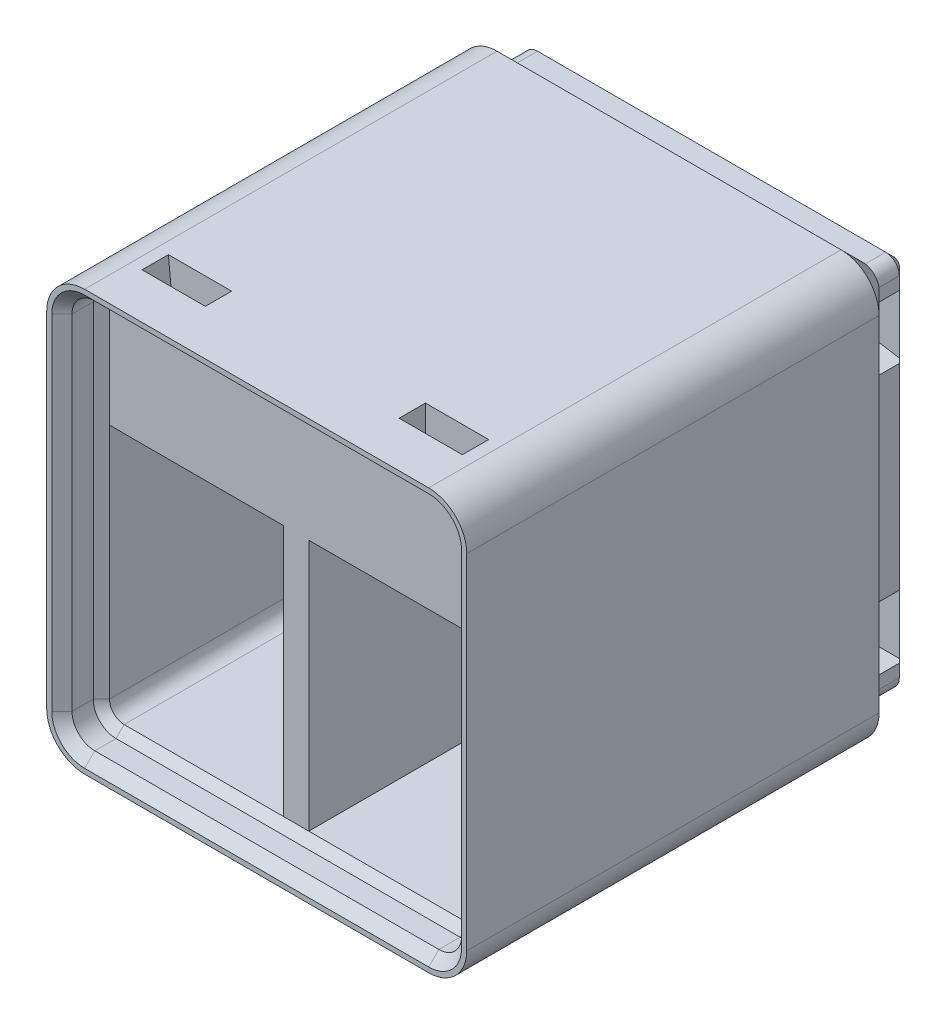
SolidWorks part; units mm, degrees
ref_plane "Front Plane" through (0, 0, 0) normal (0, 0, 1) x (1, 0, 0)
ref_plane "Top Plane" through (0, 0, 0) normal (0, 1, 0) x (1, 0, 0)
ref_plane "Right Plane" through (0, 0, 0) normal (1, 0, 0) x (0, 0, -1)
sketch "Sketch1" plane through (0, 0, 0) normal (0, 0, 1) x (1, 0, 0)
  line L1 (18.55, 18.55) -> (-18.55, 18.55)
  line L2 (18.55, 18.55) -> (18.55, -18.55)
  line L3 (18.55, -18.55) -> (-18.55, -18.55)
  line L4 (-18.55, 18.55) -> (-18.55, -18.55)
  line L5 (18.55, 18.55) -> (-18.55, -18.55) construction
  line L6 (18.55, -18.55) -> (-18.55, 18.55) construction
  point P0 (0, 0)
  dimension "D1" = 37.1
extrude "Boss-Extrude1" add sketch "Sketch1" along normal blind 2.6
sketch "Sketch2" plane through (0, 0, 2.6) normal (0, 0, 1) x (1, 0, 0)
  line L1 (-20.75, 20.75) -> (20.75, 20.75)
  line L2 (-20.75, 20.75) -> (-20.75, -20.75)
  line L3 (-20.75, -20.75) -> (20.75, -20.75)
  line L4 (20.75, 20.75) -> (20.75, -20.75)
  line L5 (-20.75, 20.75) -> (20.75, -20.75) construction
  line L6 (-20.75, -20.75) -> (20.75, 20.75) construction
  point P0 (0, 0)
  dimension "D1" = 41.5
extrude "Boss-Extrude2" add sketch "Sketch2" along normal blind 2.4
sketch "Sketch8" plane through (0, 0, 2.6) normal (0, 0, -1) x (-1, 0, 0)
  line L0 (-18.55, 18.55) -> (-18.55, 5.0094) construction
  line L1 (-18.55, -18.55) -> (-18.55, 18.55) construction
  line L2 (-14.8915, 10.3) -> (-18.55, 9.7)
  line L8 (12.7, 15.95) -> (-12.7, 15.95) construction
  line L9 (12.7, 9.45) -> (-12.7, 9.45) construction
  line L11 (-12.7, 15.95) -> (-18.55, 15.95)
  line L12 (-12.7, 12.7) -> (-12.7, -12.7)
  line L13 (-12.7, -12.7) -> (12.7, -12.7)
  line L14 (12.7, -12.7) -> (12.7, 12.7)
  line L15 (12.7, 12.7) -> (-12.7, 12.7)
  line L16 (-12.7, 9.45) -> (-12.7, -12.7) construction
  line L17 (-12.7, -12.7) -> (12.7, -12.7) construction
  line L18 (12.7, -12.7) -> (12.7, 12.7) construction
  line L19 (12.7, 12.7) -> (-12.7, 12.7) construction
  line L22 (-18.55, 15.95) -> (-18.55, 9.7)
  arc A0 (-12.7, 15.95) -> (-12.7, 9.45) centre (-12.7, 12.7) cw
  arc A1 (-12.7, 9.45) -> (-14.8915, 10.3) centre (-12.7, 12.7) cw
  dimension "D4" = 5.65
  dimension "D5" = 6.25
  dimension "D1" = 8.05
  dimension "D2" = 3.25
  dimension "D3" = 3.25
extrude "Base Magnet Slot" cut sketch "Sketch8" against normal blind 0.4 and the other way blind 2.2
fillet "Fillet1" radius 1.35 4 edges at (18.55, 18.55, 1.3) (18.55, -18.55, 1.3) (-18.55, -18.55, 1.3) (-18.55, 18.55, 1.3)
fillet "Fillet2" radius 3.75 4 edges at (20.75, -20.75, 3.8) (20.75, 20.75, 3.8) (-20.75, -20.75, 3.8) (-20.75, 20.75, 3.8)
chamfer "Chamfer1" distance 0.8 angle 45 8 edges at (-18.1546, 18.1546, 0) (-18.55, 0, 0) (-18.1546, -18.1546, 0) (0, -18.55, 0) (18.1546, -18.1546, 0) (18.55, 0, 0) (18.1546, 18.1546, 0) (0, 18.55, 0)
chamfer "Chamfer2" distance 2.4 angle 45 8 edges at (20.75, 0, 2.6) (19.6517, 19.6517, 2.6) (19.6517, -19.6517, 2.6) (0, 20.75, 2.6) (0, -20.75, 2.6) (-19.6517, 19.6517, 2.6) (-19.6517, -19.6517, 2.6) (-20.75, 0, 2.6)
sketch "Sketch4" plane through (0, 0, 0) normal (0, 0, -1) x (-1, 0, 0)
  line L9 (-12.7, -17) -> (-12.7, 17)
  line L10 (-12.7, -17) -> (-12.7, 17) construction
  line L12 (-17, 12.7) -> (17, 12.7)
  line L13 (-17, 12.7) -> (17, 12.7) construction
  circle A0 centre (-12.7, 12.7) radius 3.25
  circle A1 centre (12.7, 12.7) radius 3.25
  circle A2 centre (12.7, -12.7) radius 3.25
  circle A3 centre (-12.7, -12.7) radius 3.25
  dimension "D3" = 6.5
  dimension "D1" = 8.05
  dimension "D2" = 8.05
  dimension "D4" = 2
mirror "Mirror1" about plane through (0, 0, 0) normal (0, 1, 0) of "Base Magnet Slot"
mirror "Mirror2" about plane through (0, 0, 0) normal (1, 0, 0) of "Mirror1"
sketch "Sketch10" plane through (0, 0, 0) normal (0, 0, -1) x (-1, 0, 0)
  line L0 (-12.7, 12.7) -> (-7.7, 12.7) construction
  line L1 (-17, 12.7) -> (17, 12.7) construction
  line L2 (22.825, 0) -> (-22.825, 0) construction
  line L3 (-12.7, 13.7) -> (-7.7, 13.7)
  line L4 (-12.7, 11.7) -> (-7.7, 11.7)
  line L5 (-12.7, -12.7) -> (-7.7, -12.7) construction
  line L6 (-12.7, -13.7) -> (-7.7, -13.7)
  line L7 (-12.7, -11.7) -> (-7.7, -11.7)
  line L8 (0, 22.825) -> (0, -22.825) construction
  line L9 (12.7, 12.7) -> (7.7, 12.7) construction
  line L10 (12.7, 13.7) -> (7.7, 13.7)
  line L11 (12.7, 11.7) -> (7.7, 11.7)
  line L12 (12.7, -12.7) -> (7.7, -12.7) construction
  line L13 (12.7, -13.7) -> (7.7, -13.7)
  line L14 (12.7, -11.7) -> (7.7, -11.7)
  arc A0 (-12.7, 13.7) -> (-12.7, 11.7) centre (-12.7, 12.7) ccw
  arc A1 (-7.7, 11.7) -> (-7.7, 13.7) centre (-7.7, 12.7) ccw
  arc A2 (-12.7, -13.7) -> (-12.7, -11.7) centre (-12.7, -12.7) cw
  arc A3 (-7.7, -11.7) -> (-7.7, -13.7) centre (-7.7, -12.7) cw
  arc A4 (12.7, 13.7) -> (12.7, 11.7) centre (12.7, 12.7) cw
  arc A5 (7.7, 11.7) -> (7.7, 13.7) centre (7.7, 12.7) cw
  arc A6 (12.7, -13.7) -> (12.7, -11.7) centre (12.7, -12.7) ccw
  arc A7 (7.7, -11.7) -> (7.7, -13.7) centre (7.7, -12.7) ccw
  point P7 (-10.2, 12.7)
  point P14 (-10.2, -12.7)
  point P23 (10.2, 12.7)
  point P30 (10.2, -12.7)
extrude "Base Magnet Removal Slot" cut sketch "Sketch10" against normal up to surface (3 mm away) up to face at (15.1414, 12.5749, 3)
sketch "Sketch5" plane through (0, 0, 5) normal (0, 0, 1) x (1, 0, 0)
  line L0 (-20.75, -17) -> (-20.75, 17)
  line L1 (-20.75, -17) -> (-20.75, 17)
  line L8 (-18.45, -17) -> (-18.45, 17)
  line L9 (-17, 18.45) -> (17, 18.45)
  line L10 (18.45, 17) -> (18.45, -17)
  line L11 (17, -18.45) -> (-17, -18.45)
  line L12 (20.75, 17) -> (20.75, -17)
  line L13 (17, -20.75) -> (-17, -20.75)
  line L15 (-17, 20.75) -> (17, 20.75)
  line L18 (-17, 20.75) -> (17, 20.75) construction
  line L19 (20.75, 17) -> (20.75, -17) construction
  line L20 (17, -20.75) -> (-17, -20.75) construction
  line L22 (20.75, 17) -> (20.75, -17)
  line L23 (17, -20.75) -> (-17, -20.75)
  line L25 (-17, 20.75) -> (17, 20.75)
  arc A8 (-17, 18.45) -> (-18.45, 17) centre (-17, 17) ccw
  arc A9 (18.45, 17) -> (17, 18.45) centre (17, 17) ccw
  arc A10 (17, -18.45) -> (18.45, -17) centre (17, -17) ccw
  arc A11 (-18.45, -17) -> (-17, -18.45) centre (-17, -17) ccw
  arc A12 (17, -20.75) -> (20.75, -17) centre (17, -17) ccw
  arc A13 (-20.75, -17) -> (-17, -20.75) centre (-17, -17) ccw
  arc A14 (-17, 20.75) -> (-20.75, 17) centre (-17, 17) ccw
  arc A15 (20.75, 17) -> (17, 20.75) centre (17, 17) ccw
  arc A18 (-17, 20.75) -> (-20.75, 17) centre (-17, 17) ccw construction
  arc A19 (20.75, 17) -> (17, 20.75) centre (17, 17) ccw construction
  arc A20 (17, -20.75) -> (20.75, -17) centre (17, -17) ccw construction
  arc A21 (-20.75, -17) -> (-17, -20.75) centre (-17, -17) ccw construction
  arc A24 (17, -20.75) -> (20.75, -17) centre (17, -17) ccw
  arc A25 (-20.75, -17) -> (-17, -20.75) centre (-17, -17) ccw
  arc A26 (-17, 20.75) -> (-20.75, 17) centre (-17, 17) ccw
  arc A27 (20.75, 17) -> (17, 20.75) centre (17, 17) ccw
  dimension "D1" = 2.3
extrude "Boss-Extrude3" add sketch "Sketch5" along normal blind 36.85
sketch "Sketch12" plane through (0, 0, 41.85) normal (0, 0, 1) x (1, 0, 0)
  line L1 (18.45, -17) -> (18.45, 17) construction
  line L2 (17, 6.45) -> (-17, 6.45)
  line L3 (18.45, 6.45) -> (-18.45, 6.45)
  line L4 (17, 18.45) -> (-17, 18.45) construction
  line L5 (-18.45, 17) -> (-18.45, -17) construction
  line L6 (18.45, 6.45) -> (18.45, 17)
  line L7 (17, 18.45) -> (-17, 18.45)
  line L8 (-18.45, 17) -> (-18.45, 6.45)
  arc A0 (18.45, 17) -> (17, 18.45) centre (17, 17) ccw construction
  arc A1 (-17, 18.45) -> (-18.45, 17) centre (-17, 17) ccw construction
  arc A2 (18.45, 17) -> (17, 18.45) centre (17, 17) ccw
  arc A3 (-17, 18.45) -> (-18.45, 17) centre (-17, 17) ccw
  dimension "D1" = 12
extrude "Boss-Extrude5" add sketch "Sketch12" against normal blind 12
chamfer "Chamfer3" distance 11 angle 45 1 edges at (0, 6.45, 29.85)
fillet "Fillet3" radius 20 1 edges at (0, -18.45, 5) tangent propagation no
ref_plane "Plane1" through (0, 0, 41.25) normal (0, 0, 1) x (1, 0, 0)
sketch "Sketch13" plane through (0, 0, 41.25) normal (0, 0, 1) x (1, 0, 0)
  line L0 (-20.75, 17) -> (-20.75, -17) construction
  line L1 (17, 20.75) -> (-17, 20.75) construction
  line L2 (-9.575, 12.7) -> (-9.575, 20.75)
  line L3 (-9.575, 20.75) -> (-15.825, 20.75)
  line L4 (-15.825, 20.75) -> (-15.225, 14.5412)
  line L5 (-12.7, 12.7) -> (-12.7, -2.3) construction
  line L7 (-11.7, 9.7393) -> (-11.7, -2.3)
  line L8 (-13.7, 9.7393) -> (-13.7, -2.3)
  arc A0 (-15.225, 14.5412) -> (-13.7, 9.7393) centre (-12.7, 12.7) ccw
  arc A2 (-13.7, -2.3) -> (-11.7, -2.3) centre (-12.7, -2.3) ccw
  arc A3 (-11.7, 9.7393) -> (-9.575, 12.7) centre (-12.7, 12.7) ccw
  point P12 (-12.7, 10.2)
  dimension "D1" = 8.05
  dimension "D2" = 8.05
  dimension "D3" = 5.65
  dimension "D4" = 2
  dimension "D5" = 15
extrude "Top Magnet Slot" cut sketch "Sketch13" against normal blind 2.6
mirror "Mirror3" about plane through (0, 0, 0) normal (1, 0, 0) of "Top Magnet Slot"
sketch "Sketch11" plane through (0, 0, 41.85) normal (0, 0, 1) x (1, 0, 0)
  line L0 (-17, -20.75) -> (17, -20.75) construction
  line L1 (20.75, -17) -> (20.75, 17) construction
  line L2 (17, 20.75) -> (-17, 20.75) construction
  line L3 (-17, -20.75) -> (17, -20.75)
  line L4 (20.75, -17) -> (20.75, 17)
  line L5 (17, 20.75) -> (-17, 20.75)
  line L6 (-20.75, 17) -> (-20.75, -17) construction
  line L7 (-20.75, 17) -> (-20.75, -17)
  line L8 (-17, -19.25) -> (17, -19.25)
  line L9 (19.25, -17) -> (19.25, 17)
  line L10 (17, 19.25) -> (-17, 19.25)
  line L11 (-19.25, 17) -> (-19.25, -17)
  arc A0 (-20.75, -17) -> (-17, -20.75) centre (-17, -17) ccw construction
  arc A1 (17, -20.75) -> (20.75, -17) centre (17, -17) ccw construction
  arc A2 (20.75, 17) -> (17, 20.75) centre (17, 17) ccw construction
  arc A3 (-17, 20.75) -> (-20.75, 17) centre (-17, 17) ccw construction
  arc A4 (-20.75, -17) -> (-17, -20.75) centre (-17, -17) ccw
  arc A5 (17, -20.75) -> (20.75, -17) centre (17, -17) ccw
  arc A6 (20.75, 17) -> (17, 20.75) centre (17, 17) ccw
  arc A7 (-17, 20.75) -> (-20.75, 17) centre (-17, 17) ccw
  arc A8 (17, -19.25) -> (19.25, -17) centre (17, -17) ccw
  arc A9 (19.25, 17) -> (17, 19.25) centre (17, 17) ccw
  arc A10 (-17, 19.25) -> (-19.25, 17) centre (-17, 17) ccw
  arc A11 (-19.25, -17) -> (-17, -19.25) centre (-17, -17) ccw
  dimension "D1" = 1.5
extrude "Boss-Extrude4" add sketch "Sketch11" along normal blind 3.9
chamfer "Chamfer4" distance 0.8 angle 45 8 edges at (-18.591, 18.591, 41.85) (-19.25, 0, 41.85) (-18.591, -18.591, 41.85) (0, -19.25, 41.85) (18.591, -18.591, 41.85) (19.25, 0, 41.85) (18.591, 18.591, 41.85) (0, 19.25, 41.85)
chamfer "Chamfer5" distance 1 angle 45 8 edges at (0, -19.25, 45.75) (18.591, -18.591, 45.75) (-18.591, -18.591, 45.75) (19.25, 0, 45.75) (-19.25, 0, 45.75) (18.591, 18.591, 45.75) (-18.591, 18.591, 45.75) (0, 19.25, 45.75)
sketch "Sketch14" plane through (0, 0, 0) normal (0, 0, -1) x (-1, 0, 0)
  line L0 (17.2, 17.75) -> (-17.2, 17.75) construction
  line L1 (-3, -15.75) -> (3, -15.75)
  line L2 (-3, -15.75) -> (-3, -3)
  line L3 (-3, 15.75) -> (3, 15.75)
  line L4 (3, -15.75) -> (3, -3)
  line L5 (-3, -15.75) -> (3, 15.75) construction
  line L6 (-3, 15.75) -> (3, -15.75) construction
  line L7 (-17.75, 17.2) -> (-17.75, -17.2) construction
  line L8 (-15.75, 3) -> (-3, 3)
  line L9 (-15.75, 3) -> (-15.75, -3)
  line L10 (-15.75, -3) -> (-3, -3)
  line L11 (15.75, 3) -> (15.75, -3)
  line L12 (-15.75, 3) -> (15.75, -3) construction
  line L13 (-15.75, -3) -> (15.75, 3) construction
  line L14 (-3, 3) -> (-3, 15.75)
  line L16 (3, 3) -> (15.75, 3)
  line L17 (3, 3) -> (3, 15.75)
  line L19 (3, -3) -> (15.75, -3)
  point P0 (0, 0)
  point P10 (0, 0)
  dimension "D1" = 6
  dimension "D2" = 2
  dimension "D3" = 2
extrude "Cut-Extrude2" cut sketch "Sketch14" against normal blind 3
fillet "Fillet4" radius 1 36 edges at (-9.375, -3, 0) (9.375, -3, 0) (-3, 9.375, 0) (-15.75, 0, 0) (0, -15.75, 0) (15.75, 0, 0) (0, 15.75, 0) (9.375, -3, 3) (-3, -9.375, 3) (-3, 9.375, 3) (3, 9.375, 3) (-9.375, 3, 0) (-3, -9.375, 0) (3, -9.375, 0) (9.375, 3, 0) (3, 9.375, 0) (0, -15.75, 3) (3, -9.375, 3) (3, -3, 1.5) (-15.75, 0, 3) (-9.375, -3, 3) (-9.375, 3, 3) (0, 15.75, 3) (9.375, 3, 3) (15.75, 0, 3) (-3, -3, 1.5) (-3, 3, 1.5) (3, 3, 1.5) (-15.75, 3, 1.5) (-15.75, -3, 1.5) (-3, -15.75, 1.5) (3, -15.75, 1.5) (15.75, -3, 1.5) (-3, 15.75, 1.5) (3, 15.75, 1.5) (15.75, 3, 1.5)
ref_plane "Midplane" through (0, 0, 0) normal (1, 0, 0) x (0, 0, -1)
sketch "Sketch15" plane through (0, 0, 0) normal (1, 0, 0) x (0, 0, -1)
  line L0 (-41.85, -18.45) -> (-25, -18.45) construction
  line L1 (-41.85, -17) -> (-41.85, -18.45) construction
  line L2 (-41.85, 6.45) -> (-41.85, -17) construction
  line L3 (-30.3, 17) -> (-40.85, 6.45) construction
  line L5 (-41.85, -18.45) -> (-25, -18.45)
  line L6 (-41.85, -17) -> (-41.85, -18.45)
  line L7 (-41.85, 6.45) -> (-41.85, -17)
  line L8 (-30.3, 17) -> (-40.85, 6.45)
  line L10 (-40.85, 6.45) -> (-41.85, 6.45) construction
  line L11 (-29.85, 18.45) -> (-5, 18.45) construction
  line L12 (-40.85, 6.45) -> (-41.85, 6.45)
  line L13 (-29.85, 18.45) -> (-5, 18.45)
  line L14 (-30.3, 17) -> (-29.85, 18.45)
  line L16 (-5, 1.55) -> (-5, 18.45)
  arc A0 (-17.5235, -17) -> (-5, 1.55) centre (-25, 1.55) ccw construction
  arc A1 (-25, -18.45) -> (-17.5235, -17) centre (-25, 1.55) ccw construction
  arc A2 (-17.5235, -17) -> (-5, 1.55) centre (-25, 1.55) ccw
  arc A3 (-25, -18.45) -> (-17.5235, -17) centre (-25, 1.55) ccw
extrude "Boss-Extrude6" add sketch "Sketch15" along normal blind 1.25 and the other way blind 1.25
equation "\"D2@Sketch4\"=\"D1@Sketch4\""
equation "\"D2@Sketch13\"=\"D1@Sketch13\""
